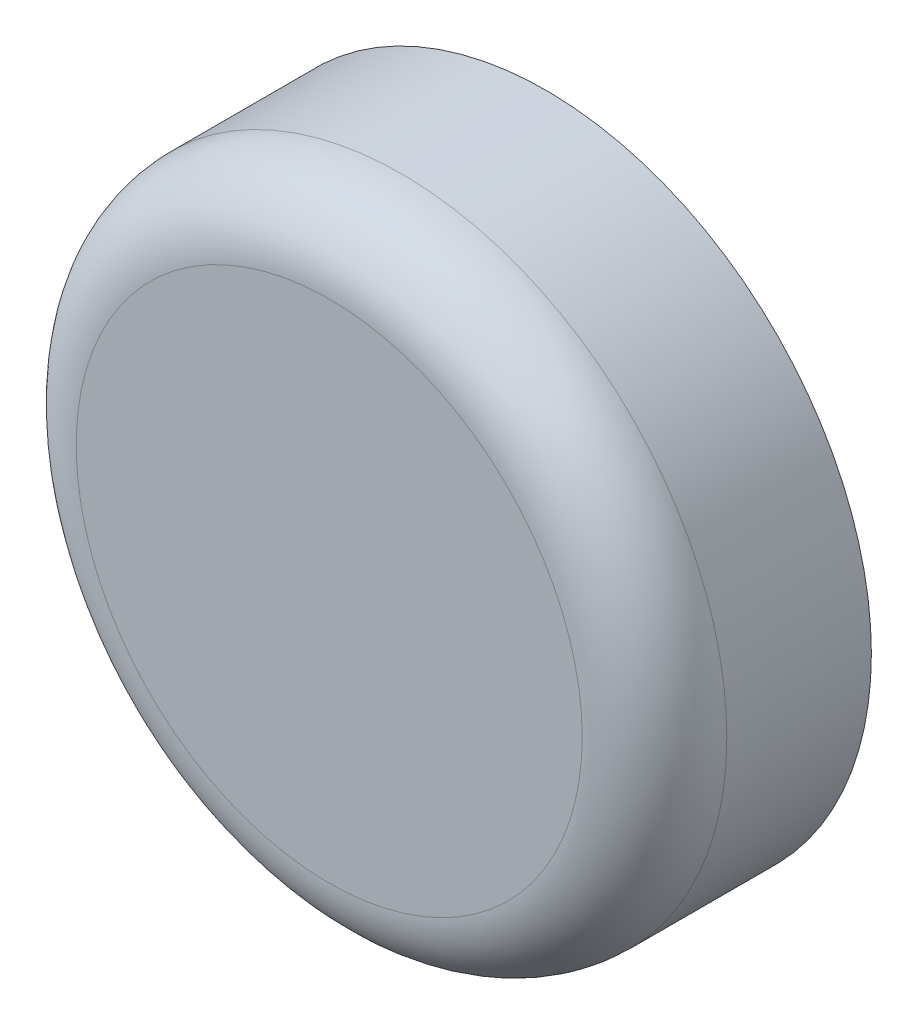
SolidWorks part; units mm, degrees
ref_plane "Plan de face" through (0, 0, 0) normal (0, 0, 1) x (1, 0, 0)
ref_plane "Plan de dessus" through (0, 0, 0) normal (0, 1, 0) x (1, 0, 0)
ref_plane "Plan de droite" through (0, 0, 0) normal (1, 0, 0) x (0, 0, -1)
sketch "Esquisse1" plane through (0, 0, 0) normal (0, 0, 1) x (1, 0, 0)
  circle A0 centre (0, 0) radius 45
  dimension "D1" = 90
extrude "Boss.-Extru.1" add sketch "Esquisse1" along normal blind 30
fillet "Congé1" radius 10 1 edges at (45, 0, 30)
sketch "Esquisse3" plane through (0, 0, 0) normal (0, 0, -1) x (-1, 0, 0)
  circle A0 centre (0, 0) radius 40
  circle A1 centre (0, 0) radius 3.15
  circle A2 centre (0, 0) radius 7
  dimension "D1" = 80
  dimension "D2" = 6.3
  dimension "D3" = 14
extrude "Enlèv. mat.-Extru.1" cut sketch "Esquisse3" against normal blind 15 contours A0 A2 | A1 region at (38.8686, 0, 0) region at (0, 0, 0)
fillet "Congé2" radius 10 1 edges at (-40, 0, 15)
fillet "Congé3" radius 5 1 edges at (-7, 0, 15)
